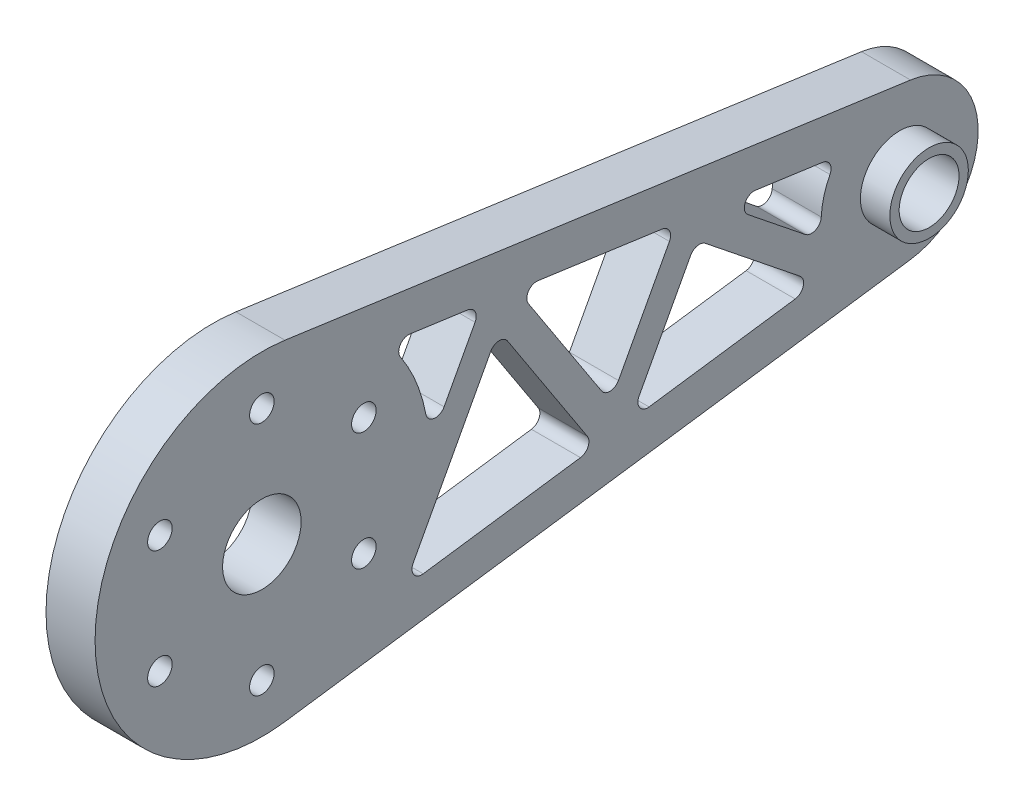
SolidWorks part; units mm, degrees
material "ABS"
ref_plane "前视基准面" through (0, 0, 0) normal (0, 0, 1) x (1, 0, 0)
ref_plane "上视基准面" through (0, 0, 0) normal (0, 1, 0) x (1, 0, 0)
ref_plane "右视基准面" through (0, 0, 0) normal (1, 0, 0) x (0, 0, -1)
other "Configuration Table"
sketch "草图1" plane through (0, 0, 0) normal (1, 0, 0) x (0, 0, -1)
  line L0 (0, 0) -> (-65, 0) construction
  line L1 (-62.6462, 16.8363) -> (1.1077, 7.9229)
  line L2 (-62.6462, -16.8363) -> (1.1077, -7.9229)
  line L3 (-65, 0) -> (-65, 12) construction
  circle A0 centre (0, 0) radius 5.1
  arc A1 (-62.6462, 16.8363) -> (-62.6462, -16.8363) centre (-65, 0) ccw
  arc A2 (1.1077, -7.9229) -> (1.1077, 7.9229) centre (0, 0) ccw
  circle A3 centre (-65, 0) radius 12 construction
  circle A4 centre (-65, 12) radius 1.25
  circle A5 centre (-54.6077, 6) radius 1.25
  circle A6 centre (-54.6077, -6) radius 1.25
  circle A7 centre (-65, -12) radius 1.25
  circle A8 centre (-75.3923, -6) radius 1.25
  circle A9 centre (-75.3923, 6) radius 1.25
  circle A10 centre (-65, 0) radius 4
  point P23 (-65, 0)
  dimension "D2" = 10.2
  dimension "D3" = 8
  dimension "D4" = 34
  dimension "D5" = 24
  dimension "D6" = 2.5
  dimension "D8" = 8
  dimension "D1" = 65
  dimension "D7" = 6
extrude "凸台-拉伸1" add sketch "草图1" along normal blind 5
sketch "草图3" plane through (5, 0, 0) normal (1, 0, 0) x (0, 0, -1)
  circle A0 centre (0, 0) radius 3.05
  circle A1 centre (0, 0) radius 5.1 construction
  circle A2 centre (0, 0) radius 5.1
  dimension "D1" = 6.1
extrude "凸台-拉伸2" add sketch "草图3" against normal blind 5
sketch "草图4" plane through (5, 0, 0) normal (1, 0, 0) x (0, 0, -1)
  line L0 (-52.3511, -11.358) -> (-41.0081, 9.7722)
  line L1 (-41.0081, 9.7722) -> (-29.3293, -8.1394)
  line L2 (-29.3293, -8.1394) -> (-21.2007, 7.0029)
  line L3 (-21.2007, 7.0029) -> (-6.3076, -4.9208)
  line L4 (-51.0294, -12.0675) -> (-40.8829, 6.8339)
  line L5 (-40.8829, 6.8339) -> (-29.2042, -11.0777)
  line L6 (0.5538, 3.9615) -> (-63.2, 12.8748)
  line L7 (-6.3076, 4.9208) -> (-52.3511, 11.358)
  line L8 (-29.2042, -11.0777) -> (-20.7315, 4.7057)
  line L9 (-63.2, -12.8748) -> (0.5538, -3.9615)
  line L10 (-52.3511, -11.358) -> (-6.3076, -4.9208)
  line L11 (-20.7315, 4.7057) -> (-7.2451, -6.0917)
  line L12 (-53.6727, -10.6486) -> (-41.1332, 12.7105)
  line L13 (-41.1332, 12.7105) -> (-29.4545, -5.2011)
  line L14 (-29.4545, -5.2011) -> (-21.67, 9.3002)
  line L15 (-21.67, 9.3002) -> (-5.3701, -3.7498)
  arc A0 (-6.3076, 4.9208) -> (-6.3076, -4.9208) centre (0, 0) ccw
  arc A1 (-52.3511, -11.358) -> (-52.3511, 11.358) centre (-65, 0) ccw
  arc A2 (-62.6462, 16.8363) -> (-62.6462, -16.8363) centre (-65, 0) ccw construction
  arc A3 (1.1077, -7.9229) -> (1.1077, 7.9229) centre (0, 0) ccw construction
  dimension "D1" = 4
  dimension "D3" = 20
  dimension "D2" = 4
  dimension "D4" = 1.5
  dimension "D5" = 1.5
extrude "切除-拉伸1" cut sketch "草图4" against normal blind 39 contours A1 L12 L7 | L4 L10 L5 | L13 L14 L7 | L11 L8 L10 | A0 L7 L15 region at (5, -4.2119, 40.7879) region at (5, 7.3676, 47.1954) region at (5, 3.84, 30.4255) region at (5, -2.7943, 18.857) region at (5, 3.3895, 11.1261)
fillet "圆角1" radius 1 15 edges at (2.5, 4.9208, 6.3076) (2.5, 11.358, 52.3511) (2.5, 6.5964, 18.2929) (2.5, -1.8105, 7.7924) (2.5, -5.2064, 8.3509) (2.5, 4.7057, 20.7315) (2.5, -7.8821, 27.4887) (2.5, 7.2243, 22.7843) (2.5, 9.4967, 39.0378) (2.5, -5.2011, 29.4545) (2.5, 6.8339, 40.8829) (2.5, -8.3688, 30.9704) (2.5, -11.1007, 50.5105) (2.5, 9.9936, 42.5917) (2.5, -0.0816, 48.0002)
sketch "草图5" plane through (5, 0, 0) normal (1, 0, 0) x (0, 0, -1)
  circle A0 centre (0, 0) radius 4
  circle A1 centre (0, 0) radius 3.05 construction
  circle A2 centre (0, 0) radius 3.05
  dimension "D1" = 8
extrude "凸台-拉伸3" add sketch "草图5" along normal blind 3
extrude "凸台-拉伸4" add sketch "草图5<2>" against normal blind 3 from surface starting at face at (0, 3.791, 30.2487)
sketch "草图5<2>" plane through (5, 0, 0) normal (1, 0, 0) x (0, 0, -1) same geometry as "草图5"
